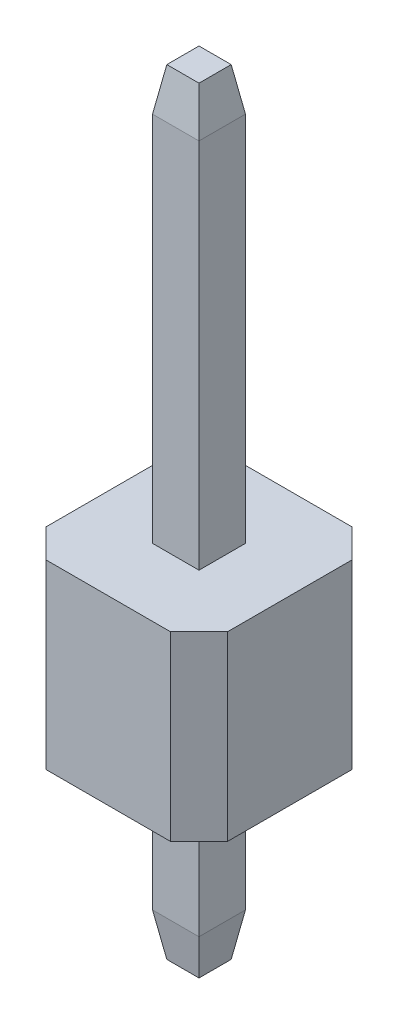
SolidWorks part; units mm, degrees
ref_plane "Спереди" through (0, 0, 0) normal (0, 0, 1) x (1, 0, 0)
ref_plane "Сверху" through (0, 0, 0) normal (0, 1, 0) x (1, 0, 0)
ref_plane "Справа" through (0, 0, 0) normal (1, 0, 0) x (0, 0, -1)
other "Configuration Table"
sketch "Эскиз1" plane through (0, 0, 0) normal (0, 1, 0) x (1, 0, 0)
  line L1 (1.27, -1.27) -> (-1.27, -1.27)
  line L2 (1.27, -1.27) -> (1.27, 1.27)
  line L3 (1.27, 1.27) -> (-1.27, 1.27)
  line L4 (-1.27, -1.27) -> (-1.27, 1.27)
  line L5 (1.27, -1.27) -> (-1.27, 1.27) construction
  line L6 (1.27, 1.27) -> (-1.27, -1.27) construction
  point P0 (0, 0)
  dimension "D1" = 2.54
  dimension "D2" = 2.54
extrude "Бобышка-Вытянуть1" add sketch "Эскиз1" along normal blind 2.54
chamfer "Фаска1" distance 0.4 angle 45 4 edges at (-1.27, 1.27, -1.27) (1.27, 1.27, -1.27) (-1.27, 1.27, 1.27) (1.27, 1.27, 1.27)
sketch "Эскиз2" plane through (0, 2.54, 0) normal (0, 1, 0) x (1, 0, 0)
  line L1 (0.325, -0.325) -> (-0.325, -0.325)
  line L2 (0.325, -0.325) -> (0.325, 0.325)
  line L3 (0.325, 0.325) -> (-0.325, 0.325)
  line L4 (-0.325, -0.325) -> (-0.325, 0.325)
  line L5 (0.325, -0.325) -> (-0.325, 0.325) construction
  line L6 (0.325, 0.325) -> (-0.325, -0.325) construction
  point P0 (0, 0)
  dimension "D1" = 0.65
extrude "Бобышка-Вытянуть2" add sketch "Эскиз2" along normal blind 5.8
extrude "Бобышка-Вытянуть3" add sketch "Эскиз2<2>" against normal blind 2.5 from surface starting at face at (0, 0, 0)
sketch "Эскиз2<2>" plane through (0, 2.54, 0) normal (0, 1, 0) x (1, 0, 0) same geometry as "Эскиз2"
chamfer "Фаска2" distance 0.6 distance2 0.1 4 edges at (-0.325, 8.34, 0) (0, 8.34, -0.325) (0, 8.34, 0.325) (0.325, 8.34, 0) first distance on face at (-0.325, 5.44, 0) first distance on face at (0, 5.44, -0.325) first distance on face at (0, 5.44, 0.325) first distance on face at (0.325, 5.44, 0)
chamfer "Фаска3" distance 0.1 distance2 0.6 4 edges at (-0.325, -2.5, 0) (0, -2.5, 0.325) (0.325, -2.5, 0) (0, -2.5, -0.325) first distance on face at (0, -2.5, 0)
